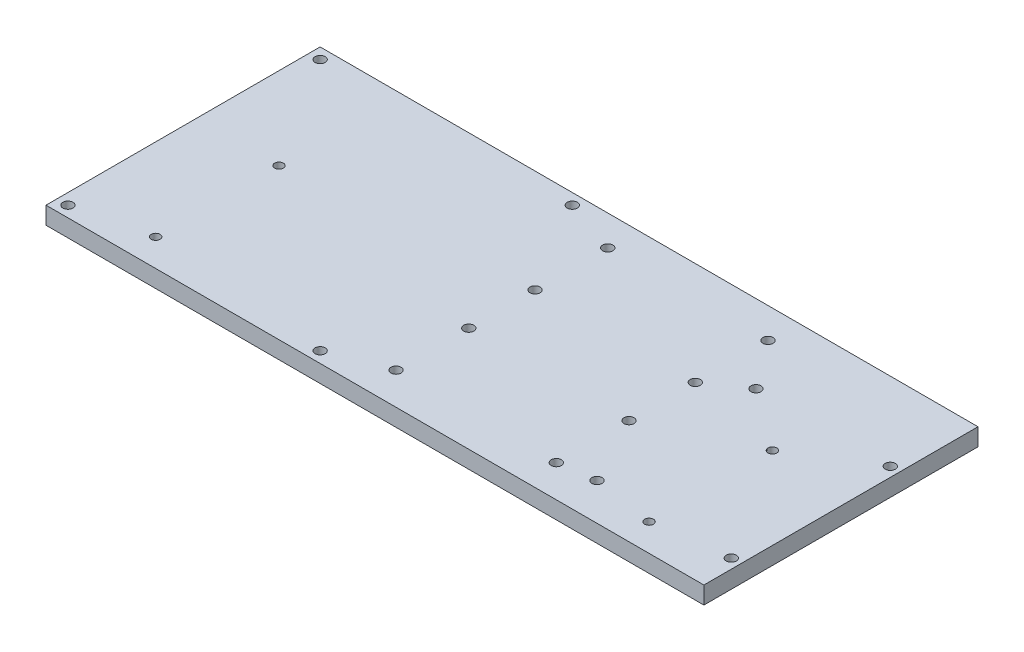
SolidWorks part; units mm, degrees
ref_plane "Front Plane" through (0, 0, 0) normal (0, 0, 1) x (1, 0, 0)
ref_plane "Top Plane" through (0, 0, 0) normal (0, 1, 0) x (1, 0, 0)
ref_plane "Right Plane" through (0, 0, 0) normal (1, 0, 0) x (0, 0, -1)
sketch "Sketch1" plane through (0, 0, 0) normal (0, 1, 0) x (1, 0, 0)
  line L1 (-120, -50) -> (120, -50)
  line L2 (-120, -50) -> (-120, 50)
  line L3 (-120, 50) -> (120, 50)
  line L4 (120, -50) -> (120, 50)
  line L5 (-120, -50) -> (120, 50) construction
  line L6 (-120, 50) -> (120, -50) construction
  point P0 (0, 0)
  dimension "D1" = 100
  dimension "D2" = 240
extrude "Boss-Extrude1" add sketch "Sketch1" along normal blind 6.35
hole_wizard "Ø3.0mm Clearance Dowel Hole2" positions "Sketch4" profile "Sketch5" hole size "Ø3.0" standard "ANSI Metric" end condition through all
sketch "Sketch4" plane through (-50.3041, 0, 69.5609) normal (0, -1, 0) x (-1, 0, 0)
  point P0 (-46.2791, 82.0009)
  point P3 (-26.3041, 115.5609)
  point P6 (-46.2791, 108.5209)
  point P9 (-46.2791, 57.8209)
  point P12 (-46.2791, 31.3009)
  point P15 (-26.3041, 23.5609)
  point P18 (65.6959, 23.5609)
  point P51 (-104.7291, 31.3009)
  point P54 (-104.7291, 57.8209)
  point P57 (-104.7291, 82.0009)
  point P60 (-104.7291, 108.5209)
  point P63 (-166.8041, 33.0609)
  point P66 (-166.8041, 91.0609)
  point P69 (-117.8041, 91.0609)
  point P72 (-117.8041, 33.0609)
  point P81 (65.6959, 115.5609)
sketch "Sketch5" plane through (-4.025, 0, -12.44) normal (1, 0, 0) x (0, 0, -1)
  line L0 (0, 0) -> (0, 6.35)
  line L1 (0, 6.35) -> (1.85, 6.35)
  line L2 (1.85, 6.35) -> (1.85, 0)
  line L3 (1.85, 0) -> (0, 0)
  line L4 (0, -6.35) -> (0, 107.95) construction
  dimension "Thru Hole Dia." = 3.7
  dimension "Thru Hole Depth" = 6.35
sketch "Sketch6" plane through (0, 6.35, 0) normal (0, 1, 0) x (1, 0, 0)
  line L0 (-120, -50) -> (120, -50) construction
  line L1 (-90, -40) -> (90, -40) construction
  line L2 (-90, -40) -> (-90, 5) construction
  line L3 (-90, 5) -> (90, 5) construction
  line L4 (90, -40) -> (90, 5) construction
  line L5 (-120, 50) -> (-120, -50) construction
  line L6 (120, -50) -> (120, 50) construction
  circle A0 centre (-90, 5) radius 1.6
  circle A1 centre (-90, -40) radius 1.6
  circle A2 centre (90, 5) radius 1.6
  circle A3 centre (90, -40) radius 1.6
  point P10 (120, 0)
  dimension "D5" = 3.2
  dimension "D1" = 10
  dimension "D2" = 55
  dimension "D3" = 30
  dimension "D4" = 30
extrude "Cut-Extrude1" cut sketch "Sketch6" against normal through all
